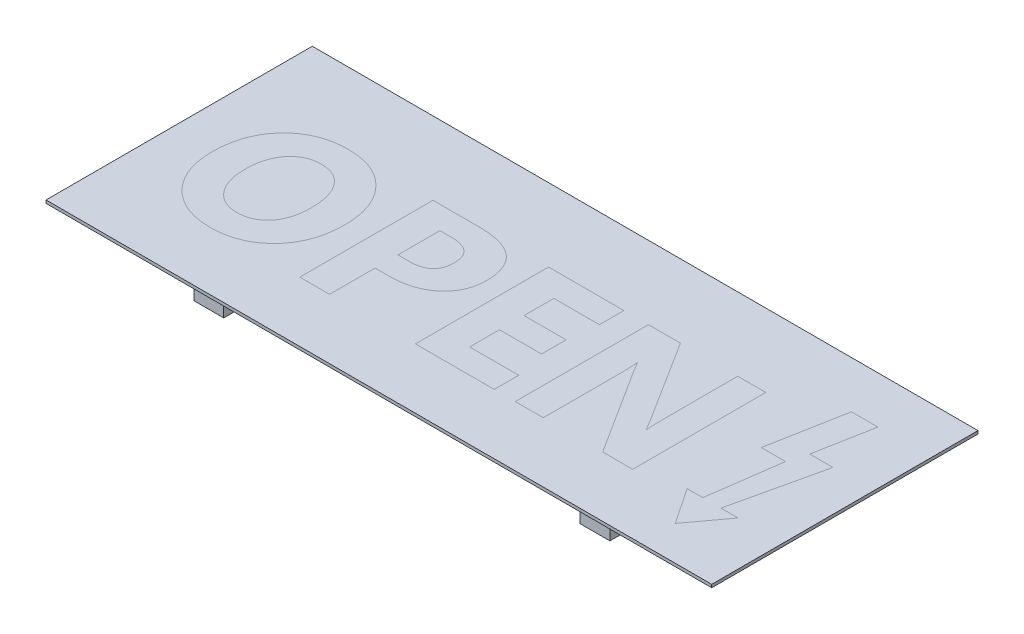
SolidWorks part; units mm, degrees
ref_plane "Front Plane" through (0, 0, 0) normal (0, 0, 1) x (1, 0, 0)
ref_plane "Top Plane" through (0, 0, 0) normal (0, 1, 0) x (1, 0, 0)
ref_plane "Right Plane" through (0, 0, 0) normal (1, 0, 0) x (0, 0, -1)
sketch "Text / Border" plane through (0, 0, 0) normal (0, 1, 0) x (1, 0, 0)
  line L0 (176.104, 65.881) -> (171.8513, 43.0301)
  line L1 (0, 0) -> (200, 0)
  line L2 (0, 0) -> (0, 80)
  line L3 (0, 80) -> (200, 80)
  line L4 (200, 0) -> (200, 80)
  line L9 (171.8513, 43.0301) -> (179.1574, 43.0301)
  line L10 (179.1574, 43.0301) -> (176.104, 21.2144)
  line L12 (181.5564, 21.2144) -> (187.7945, 48.6176)
  line L13 (187.7945, 48.6176) -> (180.8366, 48.6176)
  line L14 (180.8366, 48.6176) -> (184.0493, 65.881)
  line L15 (184.0493, 65.881) -> (176.104, 65.881)
  line L16 (171.4057, 21.2144) -> (176.104, 21.2144)
  line L17 (186.7063, 21.2144) -> (178.6682, 10.3585)
  line L18 (178.6682, 10.3585) -> (171.4057, 21.2144)
  line L19 (181.5564, 21.2144) -> (186.7063, 21.2144)
  dimension "D1" = 80
  dimension "D2" = 200
sketch "LED Guide" plane through (0, 0, 0) normal (0, 1, 0) x (1, 0, 0)
  line L0 (187.7196, 75.5) -> (198.2196, 75.5)
  line L1 (187.7196, 75.5) -> (187.7196, 15.5)
  line L2 (187.7196, 15.5) -> (198.2196, 15.5)
  line L3 (198.2196, 75.5) -> (198.2196, 15.5)
  line L4 (0, 80) -> (200, 80) construction
  dimension "D1" = 60
  dimension "D2" = 4.5
  dimension "D4" = 10.5
extrude "Body" add sketch "Text / Border" along normal blind 0.9 contours L1 L4 L3 L2 L12 L19 L17 L18 L16 L10 L9 L0 L15 L14 L13 region at (97.7358, 0, -40.0025)
extrude "Bolt" add sketch "Text / Border<9>" along normal blind 0.9 separate body contours L19 L12 L13 L14 L15 L0 L9 L10 L16 L18 L17 region at (179.5763, 0, -39.9131)
sketch "Text / Border<9>" plane through (0, 0, 0) normal (0, 1, 0) x (1, 0, 0) same geometry as "Text / Border"
sketch "Sketch6" plane through (0, 0.9, 0) normal (0, 1, 0) x (1, 0, 0)
  text T0 "<b>OPEN</b>" font "Microsoft New Tai Lue" height 40
extrude "Cut-Extrude3" cut sketch "Sketch6" against normal blind 3
extrude "Letters" add sketch "Sketch6<2>" against normal blind 0.9 separate body
sketch "Sketch6<2>" plane through (0, 0.9, 0) normal (0, 1, 0) x (1, 0, 0) same geometry as "Sketch6"
sketch "Sketch7" plane through (0, 0, 0) normal (0, -1, 0) x (1, 0, 0)
  line L0 (100, 0) -> (100, -79.3027) construction
  line L1 (0, 0) -> (200, 0) construction
  line L2 (199.7165, -39.6513) -> (0, -39.6513) construction
  line L3 (42, -6.9) -> (42, -15.9) construction
  line L4 (37.5, -6.9) -> (46.5, -6.9)
  line L5 (37.5, -6.9) -> (37.5, -15.9)
  line L6 (37.5, -15.9) -> (46.5, -15.9)
  line L7 (46.5, -6.9) -> (46.5, -15.9)
  line L8 (0, 0) -> (0, -80) construction
  dimension "D1" = 9
  dimension "D2" = 9
  dimension "D3" = 42
  dimension "D4" = 6.9
extrude "Mount Tab" add sketch "Sketch7" along normal blind 10
sketch "Sketch9" plane through (0, 0, -6.9) normal (0, 0, 1) x (1, 0, 0)
  line L0 (42, -10) -> (42, 0) construction
  line L1 (46.5, -10) -> (37.5, -10) construction
  line L2 (46.5, 0) -> (37.5, 0) construction
  line L6 (37.5, 0) -> (46.5, 0) construction
  circle A0 centre (42, -5.5) radius 1.4
  dimension "D1" = 2.8
  dimension "D2" = 5.5
extrude "M3 Screw" cut sketch "Sketch9" against normal blind 6
ref_plane "Plane1" through (100, 0, 0) normal (-1, 0, 0) x (0, 0, 1)
ref_plane "Plane2" through (0, 0, -39.6513) normal (0, 0, 1) x (1, 0, 0)
mirror "Mirror1" about plane through (100, 0, 0) normal (-1, 0, 0) of "M3 Screw", "Mount Tab"
mirror "Mirror2" about plane through (0, 0, -39.6513) normal (0, 0, 1) of "Mirror1", "M3 Screw", "Mount Tab"
